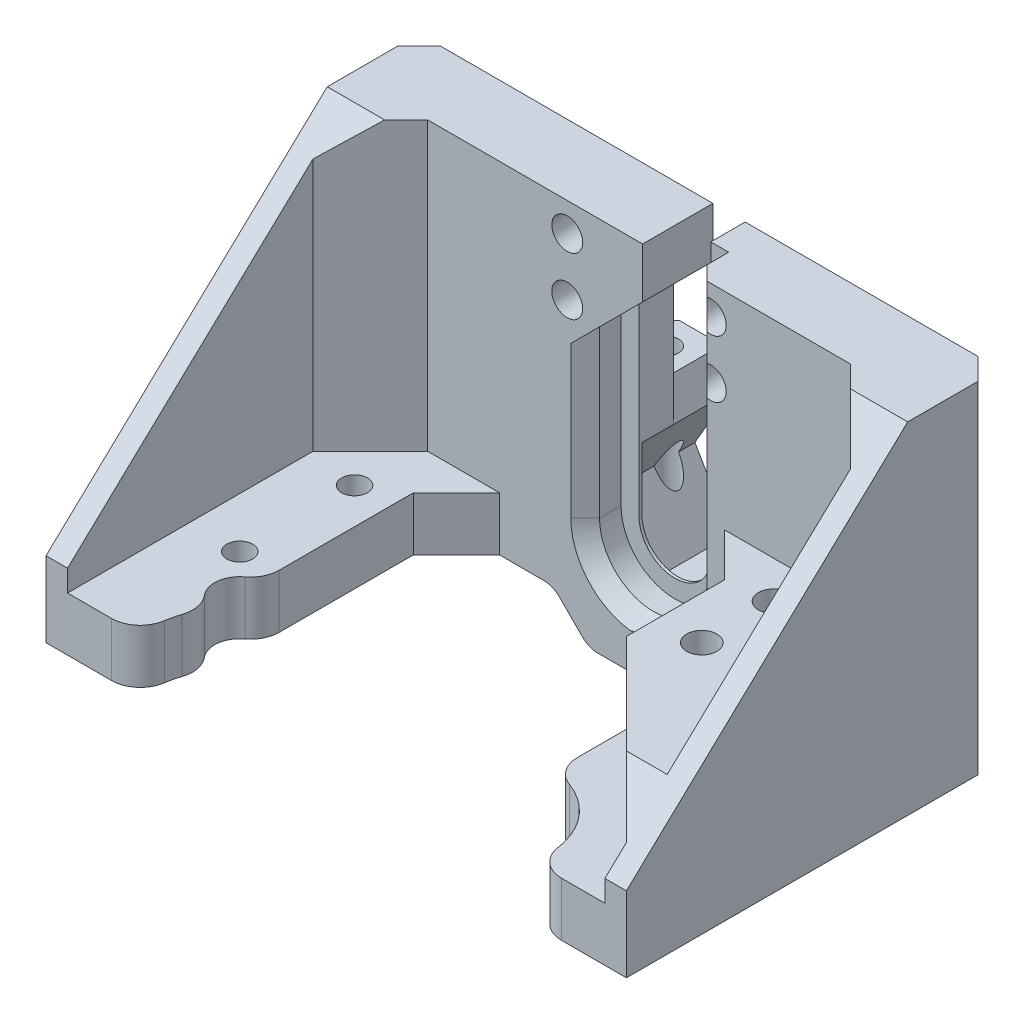
SolidWorks part; units mm, degrees
ref_plane "Front Plane" through (0, 0, 0) normal (0, 0, 1) x (1, 0, 0)
ref_plane "Top Plane" through (0, 0, 0) normal (0, 1, 0) x (1, 0, 0)
ref_plane "Right Plane" through (0, 0, 0) normal (1, 0, 0) x (0, 0, -1)
sketch "Sketch1" plane through (0, 0, 0) normal (0, 1, 0) x (1, 0, 0)
  line L0 (0, 0) -> (0, -16) construction
  line L1 (54.39, 4) -> (54.39, -6) construction
  line L2 (48.39, 9.2) -> (48.39, -33)
  line L3 (48.39, -33) -> (67.89, -33)
  line L4 (67.89, -33) -> (67.89, 19)
  line L5 (67.89, 19) -> (-7, 19)
  line L6 (-7, 19) -> (-7, -33)
  line L7 (-7, -33) -> (5, -33)
  line L8 (5, -33) -> (5, 9.2)
  line L9 (5, 9.2) -> (48.39, 9.2)
  circle A0 centre (0, 0) radius 1
  circle A1 centre (0, -16) radius 1
  circle A2 centre (54.39, 4) radius 1
  circle A3 centre (54.39, -6) radius 1
  dimension "D1" = 16
  dimension "D2" = 10
  dimension "D3" = 10
  dimension "D5" = 17
  dimension "D7" = 2
  dimension "D10" = 9.2
  dimension "D4" = 52
  dimension "D6" = 5
  dimension "D8" = 6
  dimension "D9" = 54.39
  dimension "D11" = 12
  dimension "D12" = 19.5
extrude "Boss-Extrude1" add sketch "Sketch1" along normal blind 7.5
hole_wizard "CSK for M3 Hex Socket Countersunk Head Screw1" positions "Sketch2" profile "Sketch3" countersink size "M3" standard "DIN" end condition through all
sketch "Sketch2" plane through (0, 0, 0) normal (0, -1, 0) x (-1, 0, 0)
  point P0 (0, 0)
  point P3 (0, -16)
  point P6 (-54.39, 4)
  point P9 (-54.39, -6)
sketch "Sketch3" plane through (0, 0, 0) normal (1, 0, 0) x (0, 0, -1)
  line L0 (0, 0) -> (0, 7.5)
  line L1 (0, 7.5) -> (1.8, 7.5)
  line L2 (1.8, 7.5) -> (1.8, 1.67)
  line L3 (1.8, 1.67) -> (3.47, 0)
  line L5 (3.47, 0) -> (0, 0)
  line L6 (-1.8, 1.67) -> (-3.47, 0) construction
  line L11 (0, -6.35) -> (0, 107.95) construction
  dimension "Thru Hole Dia." = 3.6
  dimension "Thru Hole Depth" = 7.5
  dimension "Near C'Sink Dia." = 6.94
  dimension "Near C'Sink Angle" = 90
sketch "Sketch4" plane through (0, 7.5, 0) normal (0, 1, 0) x (1, 0, 0)
  line L0 (67.89, -33) -> (67.89, 19) construction
  line L1 (-7, 19) -> (67.89, 19)
  line L2 (-7, 19) -> (-7, 9.2)
  line L3 (-7, 9.2) -> (67.89, 9.2)
  line L4 (67.89, 19) -> (67.89, 9.2)
  line L5 (5, 9.2) -> (48.39, 9.2) construction
extrude "Boss-Extrude2" add sketch "Sketch4" along normal blind 40
sketch "Sketch5" plane through (-7, 0, 0) normal (-1, 0, 0) x (0, 0, 1)
  line L0 (-19, 47.5) -> (-6.2, 47.5)
  line L1 (-6.2, 47.5) -> (33, 10.5)
  line L2 (33, 10.5) -> (33, 0)
  line L3 (33, 0) -> (-19, 0)
  line L4 (-19, 0) -> (-19, 47.5)
  line L5 (-9.2, 47.5) -> (-9.2, 7.5) construction
  line L6 (-9.2, 7.5) -> (33, 7.5) construction
  dimension "D1" = 3
  dimension "D2" = 3
extrude "Boss-Extrude3" add sketch "Sketch5" along normal blind 3
extrude "Boss-Extrude4" add sketch "Sketch5<2>" against normal blind 3 from surface starting at face at (67.89, 18.3333, 1.6)
sketch "Sketch5<2>" plane through (-7, 0, 0) normal (-1, 0, 0) x (0, 0, 1) same geometry as "Sketch5"
sketch "Sketch6" plane through (0, 0, 0) normal (0, -1, 0) x (1, 0, 0)
  line L0 (3, 31) -> (3, 33)
  line L1 (-10, 33) -> (5, 33) construction
  line L2 (3, 33) -> (5, 33)
  line L3 (5, 33) -> (5, 24.8356)
  line L4 (5, 33) -> (5, -9.2) construction
  circle A0 centre (13.5, 31) radius 9.5 construction
  circle A1 centre (13.5, 31) radius 9.5 construction
  arc A2 (3, 31) -> (5, 24.8356) centre (13.5, 31) ccw
  circle A3 centre (13.5, 31) radius 10.5 construction
  circle A4 centre (5.5, 21.5) radius 1.5 construction
  circle A5 centre (5.5, 21.5) radius 1.5 construction
  circle A6 centre (5.5, 21.5) radius 3.5
  circle A7 centre (47.5, 31) radius 9.5 construction
  circle A8 centre (47.5, 31) radius 9.5 construction
  circle A9 centre (47.5, 31) radius 10.5
  line M7 (5, -9.2) -> (5, 33)
  line M8 (5, 33) -> (-10, 33)
  dimension "D2" = 2
  dimension "D1" = 1
  dimension "D3" = 1
extrude "Cut-Extrude1" cut sketch "Sketch6" against normal through all contours A6 L3 L0 A2 M8 | A6 A2 M7 | A2 A6 M7 | A9 region at (4.1304, 0, 29.7376) region at (4.9724, 0, 24.917) region at (3.7405, 0, 21.4988)
fillet "Fillet1" radius 4 5 edges at (3, 3.75, 33) (4.9174, 3.75, 24.9512) (5, 3.75, 18.0359) (57.8078, 3.75, 33) (48.39, 3.75, 20.5378)
sketch "Sketch7" plane through (0, 7.5, 0) normal (0, 1, 0) x (1, 0, 0)
  line L0 (67.89, -33) -> (67.89, 9.2) construction
  line L1 (48.39, 9.2) -> (67.89, 9.2)
  line L2 (48.39, 9.2) -> (48.39, -10)
  line L3 (48.39, -10) -> (67.89, -10)
  line L4 (67.89, 9.2) -> (67.89, -10)
  circle A0 centre (54.39, -6) radius 4 construction
  dimension "D1" = 8
extrude "Boss-Extrude5" add sketch "Sketch7" along normal blind 6 from offset 5.2
hole_wizard "Ø4.2 (4.2) Diameter Hole1" positions "Sketch8" profile "Sketch10" hole size "Ø4.2" standard "DIN" end condition through all
sketch "Sketch8" plane through (0, 12.7, 0) normal (0, -1, 0) x (-1, 0, 0)
  point P0 (-54.39, -6)
  point P3 (-54.39, 4)
sketch "Sketch10" plane through (54.39, 12.7, 6) normal (1, 0, 0) x (0, 0, -1)
  line L0 (0, 0) -> (0, 34.8)
  line L1 (0, 34.8) -> (2.1, 34.8)
  line L2 (2.1, 34.8) -> (2.1, 0)
  line L5 (2.1, 0) -> (0, 0)
  line L11 (0, -6.35) -> (0, 107.95) construction
  dimension "Thru Hole Dia." = 4.2
  dimension "Thru Hole Depth" = 34.8
chamfer "Chamfer1" distance 20 angle 45 1 edges at (67.89, 15.7, 10)
chamfer "Chamfer2" distance 8 angle 45 2 edges at (-7, 27.5, -9.2) (67.89, 33.1, -9.2)
chamfer "Chamfer3" distance 3 angle 45 2 edges at (70.89, 23.75, -19) (-10, 23.75, -19)
chamfer "Chamfer4" distance 6 angle 45 3 edges at (48.39, 15.7, -9.2) (48.39, 3.75, -9.2) (5, 3.75, -9.2)
sketch "Sketch11" plane through (0, 0, -19) normal (0, 0, -1) x (-1, 0, 0)
  line L0 (-70.89, 0) -> (-70.89, 47.5) construction
  line L1 (10, 47.5) -> (10, 0) construction
  line L2 (-70.89, 0) -> (-70.89, 47.5) construction
  line L3 (10, 47.5) -> (10, 0) construction
  line L4 (-70.89, 9.4) -> (-30.445, 9.4) construction
  line L5 (-30.445, 9.4) -> (10, 9.4) construction
  line L6 (-67.89, 0) -> (7, 0) construction
  line L7 (-35.445, 9.4) -> (-35.445, 47.5)
  line L8 (-67.89, 47.5) -> (7, 47.5) construction
  line L9 (-35.445, 47.5) -> (-25.445, 47.5)
  line L10 (-25.445, 47.5) -> (-25.445, 9.4)
  arc A0 (-35.445, 9.4) -> (-25.445, 9.4) centre (-30.445, 9.4) ccw
  dimension "D1" = 9.4
  dimension "D2" = 10
extrude "Cut-Extrude2" cut sketch "Sketch11" against normal through all
sketch "Sketch13" plane through (0, 0, -19) normal (0, 0, -1) x (-1, 0, 0)
  line L0 (-25.445, 9.4) -> (-25.445, 47.5) construction
  line L1 (-35.445, 47.5) -> (-35.445, 9.4) construction
  line L2 (-25.445, 9.4) -> (-25.445, 17.3599)
  line L3 (-35.445, 17.3599) -> (-35.445, 9.4)
  arc A0 (-35.445, 17.3599) -> (-25.445, 17.3599) centre (-30.445, 9.4) ccw
  arc A1 (-35.445, 9.4) -> (-25.445, 9.4) centre (-30.445, 9.4) ccw construction
  arc A2 (-35.445, 9.4) -> (-25.445, 9.4) centre (-30.445, 9.4) ccw
extrude "Boss-Extrude7" [suppressed] add sketch "Sketch13" along normal blind 10
sketch "Sketch14" plane through (0, 0, -9.2) normal (0, 0, 1) x (1, 0, 0)
  line L0 (22.945, 9.4) -> (22.945, 47.5)
  line L1 (1, 47.5) -> (25.445, 47.5) construction
  line L2 (22.945, 47.5) -> (37.945, 47.5)
  line L3 (35.445, 47.5) -> (59.89, 47.5) construction
  line L4 (37.945, 47.5) -> (37.945, 9.4)
  arc A0 (22.945, 9.4) -> (37.945, 9.4) centre (30.445, 9.4) ccw
  dimension "D1" = 15
extrude "Cut-Extrude3" cut sketch "Sketch14" against normal blind 5
sketch "Sketch12" plane through (0, 0, -9.2) normal (0, 0, -1) x (-1, 0, 0)
  line L0 (-22.945, 47.5) -> (-30.945, 47.5)
  line L1 (-30.945, 47.5) -> (-30.945, 40.5)
  line L2 (-30.945, 40.5) -> (-22.945, 32.5)
  line L4 (-22.945, 32.5) -> (-22.945, 47.5)
  line L5 (-35.445, 47.5) -> (-35.445, 9.4) construction
  line L7 (-22.945, 47.5) -> (-22.945, 9.4) construction
  line L8 (-1, 47.5) -> (-22.945, 47.5) construction
  dimension "D1" = 45
  dimension "D2" = 4.5
  dimension "D3" = 15
extrude "Boss-Extrude6" add sketch "Sketch12" along normal up to surface (9.8 mm away) up to face at (30.445, 25.475, -19)
chamfer "Chamfer5" [suppressed] distance 3 angle 45
sketch "Sketch15" plane through (0, 0, -19) normal (0, 0, -1) x (-1, 0, 0)
  line L0 (-21.121, -2.35) -> (-39.769, -2.35)
  line L1 (-35.445, 18.0603) -> (-40.445, 9.4)
  line L2 (-40.445, 9.4) -> (-35.445, 0.7397)
  line L3 (-35.445, 0.7397) -> (-25.445, 0.7397)
  line L4 (-25.445, 0.7397) -> (-20.445, 9.4)
  line L5 (-20.445, 9.4) -> (-25.445, 18.0603)
  line L6 (-25.445, 18.0603) -> (-35.445, 18.0603)
  line L7 (-36.695, 23.0359) -> (-35.445, 18.0603)
  line L8 (-25.445, 18.0603) -> (-24.195, 23.0359)
  circle A0 centre (-30.445, 9.4) radius 10 construction
  circle A1 centre (-30.445, 9.4) radius 8.6603 construction
  arc A2 (-21.121, -2.35) -> (-39.769, -2.35) centre (-30.445, 9.4) ccw
  line M13 (-25.445, 35) -> (-25.445, 9.4)
  line M15 (-35.445, 9.4) -> (-35.445, 47.5)
  line M18 (-67.89, 0) -> (7, 0)
  dimension "D1" = 20
  dimension "D2" = 30
extrude "Boss-Extrude8" add sketch "Sketch15" along normal blind 8 contours A2 L5 L4 L3 L2 L1 M15 M18 M13 region at (30.445, 0.3782, -19)
sketch "Sketch16" plane through (0, 0, -19) normal (0, 0, -1) x (-1, 0, 0)
  line L7 (-25.445, 0.7397) -> (-20.445, 9.4)
  line L8 (-20.445, 9.4) -> (-25.445, 18.0603)
  line L9 (-25.445, 18.0603) -> (-25.445, 9.4)
  line L10 (-35.445, 9.4) -> (-35.445, 18.0603)
  line L11 (-35.445, 18.0603) -> (-40.445, 9.4)
  line L12 (-40.445, 9.4) -> (-35.445, 0.7397)
  line L13 (-35.445, 0.7397) -> (-25.445, 0.7397)
  line L14 (-25.445, 0.7397) -> (-20.445, 9.4)
  line L15 (-20.445, 9.4) -> (-25.445, 18.0603)
  line L16 (-25.445, 18.0603) -> (-25.445, 9.4)
  line L17 (-35.445, 9.4) -> (-35.445, 18.0603)
  line L18 (-35.445, 18.0603) -> (-40.445, 9.4)
  line L19 (-40.445, 9.4) -> (-35.445, 0.7397)
  line L20 (-35.445, 0.7397) -> (-25.445, 0.7397)
  arc A1 (-35.445, 9.4) -> (-25.445, 9.4) centre (-30.445, 9.4) ccw
  arc A2 (-35.445, 9.4) -> (-25.445, 9.4) centre (-30.445, 9.4) ccw
  dimension "D1" = 0
extrude "Cut-Extrude4" cut sketch "Sketch16" against normal blind 4.4
chamfer "Chamfer6" [suppressed] distance 2 angle 45
sketch "Sketch18" plane through (0, 0, -19) normal (0, 0, -1) x (-1, 0, 0)
  line L0 (-67.89, 0) -> (-42.1343, 0) construction
  line L1 (-45.445, 0) -> (-42.1343, 0)
  line L2 (-45.445, 0) -> (-45.445, 23.0359)
  line L3 (-45.445, 23.0359) -> (-36.695, 23.0359)
  line L4 (-15.445, 0) -> (-15.445, 23.0359)
  line L5 (-24.195, 23.0359) -> (-15.445, 23.0359)
  line L6 (-18.7557, 0) -> (-15.445, 0)
  arc A0 (-18.7557, 0) -> (-24.195, 23.0359) centre (-30.445, 9.4) ccw construction
  arc A1 (-36.695, 23.0359) -> (-42.1343, 0) centre (-30.445, 9.4) ccw construction
  arc A2 (-18.7557, 0) -> (-24.195, 23.0359) centre (-30.445, 9.4) ccw construction
  arc A3 (-18.7557, 0) -> (-24.195, 23.0359) centre (-30.445, 9.4) ccw
  arc A4 (-36.695, 23.0359) -> (-42.1343, 0) centre (-30.445, 9.4) ccw
  arc M5 (-24.195, 23.0359) -> (-18.7557, 0) centre (-30.445, 9.4) cw
  line M6 (-18.7557, 0) -> (7, 0)
extrude "Boss-Extrude9" add sketch "Sketch18" along normal up to surface (8 mm away) contours A4 L2 L1 | L4 M6 M5 | L5 L4 M5 | A4 L3 L2 region at (44.4739, 2.295, -19) region at (43.036, 19.8558, -19) region at (16.4161, 2.295, -19) region at (17.854, 19.8558, -19) up to face at (30.445, 10.513, -27)
sketch "Sketch17" plane through (0, 0, 0) normal (0, -1, 0) x (1, 0, 0)
  line L0 (20.445, -27) -> (20.445, -14.6) construction
  line L1 (20.445, -27) -> (20.445, -14.6) construction
  line L2 (30.445, -27) -> (30.445, -19) construction
  line L3 (45.445, -27) -> (15.445, -27) construction
  line L4 (67.89, -19) -> (45.445, -19) construction
  line L5 (30.445, -23) -> (20.445, -23) construction
  circle A0 centre (20.445, -23) radius 1
  circle A1 centre (40.445, -23) radius 1
  point P11 (30.445, -27)
  dimension "D1" = 2
extrude "Cut-Extrude5" cut sketch "Sketch17" against normal through all
hole_wizard "M3 Clearance Hole1" positions "Sketch19" profile "Sketch20" hole size "M3" standard "DIN" end condition through all
sketch "Sketch19" plane through (0, 0, 0) normal (0, -1, 0) x (-1, 0, 0)
  point P0 (-20.445, 23)
  point P3 (-40.445, 23)
sketch "Sketch20" plane through (20.445, 0, -23) normal (1, 0, 0) x (0, 0, -1)
  line L0 (0, 0) -> (0, 47.5)
  line L1 (0, 47.5) -> (1.7, 47.5)
  line L2 (1.7, 47.5) -> (1.7, 0)
  line L5 (1.7, 0) -> (0, 0)
  line L11 (0, -6.35) -> (0, 107.95) construction
  dimension "Thru Hole Dia." = 3.4
  dimension "Thru Hole Depth" = 47.5
chamfer "Chamfer9" distance 8 angle 45 2 edges at (45.445, 11.5179, -19) (15.445, 11.5179, -19)
chamfer "Chamfer7" distance 2 angle 45 4 edges at (11.445, 0, -23) (11.445, 23.0359, -23) (49.445, 23.0359, -23) (49.445, 0, -23)
chamfer "Chamfer8" distance 2 angle 45 3 edges at (22.945, 20.95, -9.2) (30.445, 1.9, -9.2) (37.945, 28.45, -9.2)
hole_wizard "Ø4.3 (4.3) Diameter Hole1" positions "Sketch22" profile "Sketch23" hole size "Ø4.3" standard "DIN" end condition up to next
sketch "Sketch22" plane through (0, 0, -19) normal (0, 0, -1) x (-1, 0, 0)
  line L1 (-45.445, 47.5) -> (-15.445, 47.5)
  line L2 (-45.445, 47.5) -> (-45.445, 31.5)
  line L3 (-45.445, 31.5) -> (-15.445, 31.5)
  line L4 (-15.445, 47.5) -> (-15.445, 31.5)
  line L5 (-67.89, 47.5) -> (-35.445, 47.5) construction
  line L6 (-30.445, 9.4) -> (-30.445, 31.5) construction
  line L7 (-20.445, 43.5) -> (-40.445, 43.5)
  point P39 (-40.445, 43.5)
  point P41 (-40.445, 35.5)
  point P43 (-20.445, 35.5)
  point P45 (-20.445, 43.5)
  dimension "D1" = 16
  dimension "D2" = 30
  dimension "D3" = 8
  dimension "D4" = 8
  dimension "D5" = 4
  dimension "D6" = 20
  dimension "D7" = 5
sketch "Sketch23" plane through (20.445, 43.5, -19) normal (1, 0, 0) x (0, 1, 0)
  line L0 (0, 0) -> (0, 9.8)
  line L1 (0, 9.8) -> (2.15, 9.8)
  line L2 (2.15, 9.8) -> (2.15, 0)
  line L5 (2.15, 0) -> (0, 0)
  line L11 (0, -6.35) -> (0, 107.95) construction
  dimension "Thru Hole Dia." = 4.3
  dimension "Thru Hole Depth" = 9.8
sketch "Sketch24" plane through (0, 0, -27) normal (0, 0, -1) x (-1, 0, 0)
  line L0 (-42.145, 0) -> (-38.745, 0) construction
  line L1 (-22.145, 0) -> (-18.745, 0) construction
  line L2 (-42.145, 0) -> (-38.745, 0) construction
  line L3 (-22.145, 0) -> (-18.745, 0) construction
  line L4 (-44.445, 0) -> (-36.445, 0) construction
  line L5 (-42.6166, 0) -> (-18.2734, 0) construction
  line L6 (-36.445, 0) -> (-36.445, -5)
  line L7 (-36.445, -5) -> (-24.445, -5)
  line L8 (-24.445, -5) -> (-24.445, 0)
  line L9 (-24.445, 0) -> (-36.445, 0)
  point P4 (-20.445, 0)
  point P9 (-40.445, 0)
  dimension "D1" = 8
  dimension "D2" = 4
  dimension "D3" = 5
extrude "Boss-Extrude10" add sketch "Sketch24" against normal up to surface (17.8 mm away) up to face at (46.9106, 22.5792, -9.2)
chamfer "Chamfer10" distance 6 angle 45 2 edges at (24.445, 0, -18.1) (36.445, 0, -18.1)
sketch "Sketch25" plane through (0, -5, 0) normal (0, -1, 0) x (1, 0, 0)
  circle A0 centre (40.445, -23) radius 3.75
  circle A1 centre (20.445, -23) radius 3.75
  dimension "D1" = 7.5
extrude "Cut-Extrude6" cut sketch "Sketch25" against normal up to surface (5 mm away) up to face at (4.7903, 0, 3.4823)
fillet "Fillet3" radius 3 4 edges at (37.445, -5, -14.975) (42.445, 0, -14.4864) (23.445, -5, -14.975) (18.445, 0, -14.5139)
